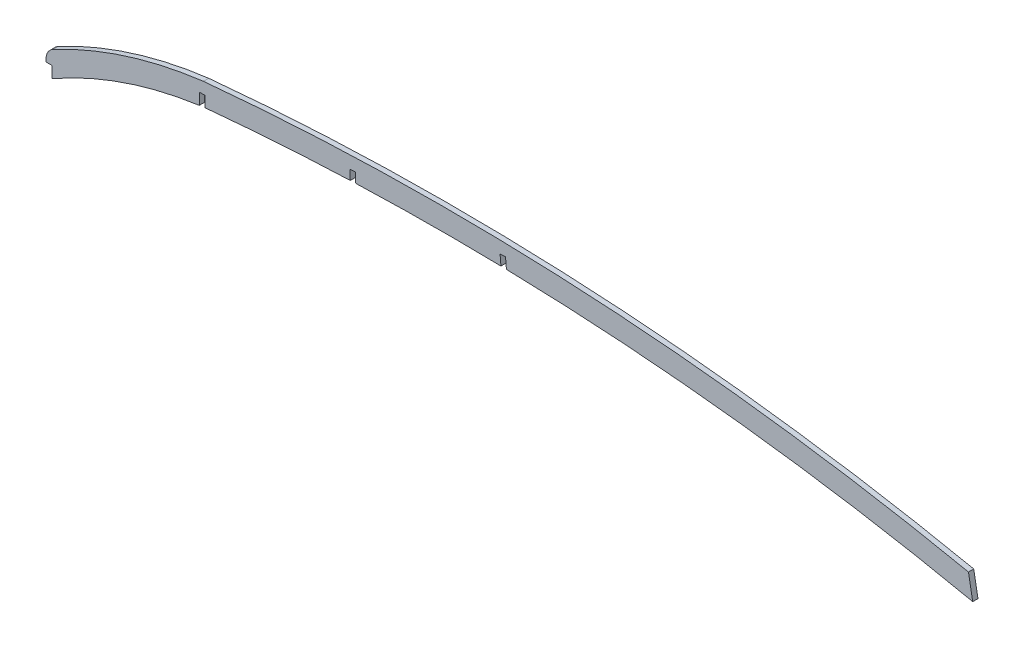
SolidWorks part; units mm, degrees
material "Balsa"
ref_plane "Front Plane" through (0, 0, 0) normal (0, 0, 1) x (1, 0, 0)
ref_plane "Top Plane" through (0, 0, 0) normal (0, 1, 0) x (1, 0, 0)
ref_plane "Right Plane" through (0, 0, 0) normal (1, 0, 0) x (0, 0, -1)
sketch "Sketch1" plane through (0, 0, 0) normal (0, 0, 1) x (1, 0, 0)
  line L0 (0, 101.6) -> (0, 100.0553)
  line L1 (0, -1.7463) -> (0, 1.7463) construction
  line L2 (0, 86.36) -> (8.1082, 86.36) construction
  line L3 (3.7499, 106.3536) -> (3.7499, -82.5359) construction
  line L4 (8.1082, 101.6) -> (0, 101.6) construction
  line L5 (92.329, 130.518) -> (92.329, 123.5672)
  line L6 (3.7499, 93.1973) -> (0, 91.0322) construction
  line L7 (0, 99.5163) -> (0, 88.039) construction
  line L8 (558.2295, 97.6273) -> (555.6382, 111.8229)
  line L9 (0, 91.0322) -> (0, 86.36) construction
  line L10 (3.7499, 93.1973) -> (3.7499, 100.0553)
  line L11 (3.7499, 100.0553) -> (0, 97.8902) construction
  line L12 (0, 97.8902) -> (0, 91.0322) construction
  line L13 (3.7499, 100.0553) -> (0, 100.0553)
  line L14 (0, 100.0553) -> (0, 97.8902) construction
  line L17 (92.3925, 137.6625) -> (92.3925, -126.4975) construction
  line L18 (95.631, 130.518) -> (95.631, 124.0109)
  line L19 (95.5675, -126.4975) -> (95.5675, 137.6625) construction
  line L20 (95.5675, 137.6297) -> (92.3925, 137.6297) construction
  line L21 (93.98, 137.6297) -> (93.98, 130.518) construction
  line L22 (92.329, 130.518) -> (95.631, 130.518)
  line L23 (92.329, 123.5672) -> (92.329, 122.506) construction
  line L24 (95.631, 124.0109) -> (95.631, 123.1918) construction
  line L26 (196.7865, -114.9693) -> (197.4984, -131.9724) construction
  line L27 (185.959, 143.6301) -> (186.671, 126.627) construction
  line L28 (193.6143, -115.1021) -> (194.3262, -132.1052) construction
  line L30 (182.7868, 143.4973) -> (183.4987, 126.4942) construction
  line L32 (185.959, 143.6301) -> (182.7868, 143.4973) construction
  line L41 (182.7868, 143.4973) -> (186.671, 126.627) construction
  line L42 (184.7289, 135.0622) -> (184.9758, 129.1656) construction
  line L43 (183.294, 129.865) -> (183.0502, 135.6897)
  line L44 (186.5939, 129.9858) -> (186.3493, 135.8278)
  line L45 (183.0502, 135.6897) -> (186.3493, 135.8278)
  line L46 (183.2948, 129.8477) -> (183.294, 129.865) construction
  line L47 (276.0995, 144.3308) -> (272.9362, 144.0585)
  line L48 (298.3406, -114.0477) -> (295.1773, -114.32)
  line L49 (274.4392, 126.5971) -> (277.6025, 126.8694)
  line L50 (272.9362, 144.0585) -> (274.4392, 126.5971)
  line L51 (295.1773, -114.32) -> (296.6804, -131.7814)
  line L52 (276.0995, 144.3308) -> (277.6025, 126.8694)
  line L53 (298.3406, -114.0477) -> (299.8437, -131.5091)
  line L54 (296.6804, -131.7814) -> (299.8437, -131.5091)
  line L57 (276.0995, 144.3308) -> (277.6025, 126.8694) construction
  line L59 (272.9362, 144.0585) -> (274.4392, 126.5971) construction
  line L60 (274.4392, 126.5971) -> (277.6025, 126.8694) construction
  line L63 (274.4392, 126.5971) -> (276.0995, 144.3308) construction
  line L64 (275.2694, 135.4639) -> (274.3291, 146.3866) construction
  line L65 (274.0318, 130.5899) -> (273.5181, 136.5576)
  line L66 (277.3525, 130.5142) -> (276.8079, 136.8408)
  line L67 (273.5181, 136.5576) -> (276.8079, 136.8408)
  line L68 (274.0627, 130.231) -> (274.0318, 130.5899) construction
  line L69 (193.6143, -115.1021) -> (196.7865, -114.9693)
  line L70 (186.671, 126.627) -> (183.4987, 126.4942)
  line L71 (194.3262, -132.1052) -> (197.4984, -131.9724)
  line L72 (185.959, 143.6301) -> (182.7868, 143.4973)
  line L73 (182.7868, 143.4973) -> (183.4987, 126.4942)
  line L74 (193.6143, -115.1021) -> (194.3262, -132.1052)
  line L75 (185.959, 143.6301) -> (186.671, 126.627)
  line L76 (276.0995, 144.3308) -> (272.9362, 144.0585)
  line L77 (194.3262, -132.1052) -> (197.4984, -131.9724) construction
  line L78 (196.7865, -114.9693) -> (197.4984, -131.9724)
  line L79 (186.671, 126.627) -> (183.4987, 126.4942) construction
  line L80 (193.6143, -115.1021) -> (196.7865, -114.9693) construction
  arc A0 (4.3005, 108.7585) -> (94.8544, 137.376) centre (127, -121.92) cw
  arc A1 (4.3005, 108.7585) -> (0, 101.6) centre (8.1082, 101.6) ccw
  arc A2 (3.7499, 93.1973) -> (0, 86.36) centre (8.1082, 86.36) ccw construction
  arc A3 (94.8544, 137.376) -> (555.6382, 111.8229) centre (240.8652, -1397) cw
  arc A4 (3.7499, 93.1973) -> (92.329, 123.5672) centre (127, -121.92) cw
  arc A5 (96.3112, 124.0967) -> (183.294, 129.865) centre (240.8652, -1397) cw
  arc A6 (10.5733, 96.9655) -> (96.3112, 124.0967) centre (127, -121.92) cw construction
  arc A7 (94.4927, 137.3434) -> (3.7499, 106.3536) centre (112.883, -64.8553) ccw construction
  arc A8 (96.3112, 124.0967) -> (552.9103, 98.7469) centre (240.8652, -1397) cw construction
  arc A9 (4.3005, 108.7585) -> (94.8544, 137.376) centre (127, -121.92) cw construction
  arc A10 (92.329, 123.5672) -> (95.631, 124.0109) centre (127, -121.92) cw construction
  arc A11 (94.8544, 137.376) -> (555.6382, 111.8229) centre (240.8652, -1397) cw construction
  arc A12 (95.631, 124.0109) -> (96.3112, 124.0967) centre (127, -121.92) cw
  arc A13 (556.7512, 105.7321) -> (99.1899, 122.2822) centre (270.5046, -1474.7614) ccw construction
  arc A14 (183.294, 129.865) -> (183.3575, 129.8673) centre (240.8652, -1397) cw construction
  arc A15 (184.9439, 129.9263) -> (185.9033, 129.9611) centre (240.8652, -1397) cw construction
  arc A16 (183.3575, 129.8673) -> (184.9439, 129.9263) centre (240.8652, -1397) cw construction
  arc A17 (185.9033, 129.9611) -> (186.5304, 129.9835) centre (240.8652, -1397) cw construction
  arc A18 (186.5939, 129.9858) -> (274.0318, 130.5899) centre (240.8652, -1397) cw
  arc A19 (186.5304, 129.9835) -> (186.5939, 129.9858) centre (240.8652, -1397) cw construction
  arc A20 (274.0957, 130.5885) -> (274.8114, 130.5728) centre (240.8652, -1397) cw construction
  arc A21 (277.3525, 130.5142) -> (558.2295, 97.6273) centre (240.8652, -1397) cw
  arc A22 (274.0318, 130.5899) -> (274.0957, 130.5885) centre (240.8652, -1397) cw construction
  arc A23 (274.8114, 130.5728) -> (277.2887, 130.5157) centre (240.8652, -1397) cw construction
  arc A24 (277.2887, 130.5157) -> (277.3525, 130.5142) centre (240.8652, -1397) cw construction
  spline S0 degree 3 poles (981.3177, 1818.2675) (1139.722, 204.4849) (873.2182, 1.0169) (565.628, -88.9106) (559.2919, -90.7077) (-121.8164, -278.7114) (-929.5333, 36.0269) (-1233.6865, -867.5095) knots -11.664502 -11.664502 -11.664502 -11.664502 0.25 0.25 0.5 0.5 27.071012 27.071012 27.071012 27.071012 only from (590.8643, -81.3536) to (514.7143, -102.4537) construction
  spline S1 degree 3 poles (1062.5522, -1662.3274) (1783.386, 752.2598) (1192.007, 51.9761) (480.6823, -110.4688) (472.1454, -112.3347) (455.0337, -115.879) (446.4591, -117.5582) (433.5613, -119.8984) (429.2558, -120.648) (422.7903, -121.7356) (420.6337, -122.0915) (417.3979, -122.6188) (416.3191, -122.7935) (329.7173, -136.7537) (244.3749, -151.8452) (-150.7518, 1789.6158) knots -20.37019 -20.37019 -20.37019 -20.37019 0.25 0.25 0.5 0.5 0.75 0.75 0.875 0.875 0.9375 0.9375 0.96875 0.96875 3.445896 3.445896 3.445896 3.445896 only from (514.7143, -102.4537) to (412.003, -123.4859) construction
  spline S2 degree 3 poles (-1526.2092, 975.8893) (-966.7298, 244.4948) (-373.5074, -121.9571) (226.7788, -133.168) (266.5142, -132.8729) (279.7628, -132.6016) (299.6408, -131.9345) (306.2677, -131.6688) (319.5231, -131.0505) (326.1536, -130.6977) (943.6584, -93.7895) (1501.3881, 309.0053) (2017.121, 1001.2295) knots -5.168103 -5.168103 -5.168103 -5.168103 0.25 0.5 0.5 0.625 0.625 0.6875 0.6875 0.75 0.75 6.511417 6.511417 6.511417 6.511417 only from (94.4926, -125.8525) to (412.003, -123.4859) construction
  spline S3 degree 3 poles (82.8406, 1879.826) (-241.5287, 509.6599) (-195.4311, -0.6421) (32.0968, -110.0953) (39.5136, -113.1375) (50.922, -117.0433) (54.7721, -118.2354) (60.6197, -119.8556) (62.5829, -120.3681) (66.5243, -121.3341) (68.5001, -121.787) (343.1899, -180.4478) (711.1357, 326.3263) (1193.75, 1513.3939) knots -7.368418 -7.368418 -7.368418 -7.368418 0.25 0.25 0.5 0.5 0.625 0.625 0.6875 0.6875 0.75 0.75 9.354609 9.354609 9.354609 9.354609 only from (3.7499, -94.8626) to (94.4926, -125.8525) construction
  spline S6 degree 3 poles (590.8643, -81.3536) (584.5771, -83.3154) (578.2709, -85.2143) (565.628, -88.9106) (559.2919, -90.7077) (540.2459, -95.9648) (527.5015, -99.2922) (514.7143, -102.4537) knots 0 0 0 0 0.25 0.25 0.5 0.5 1 1 1 1 construction
  spline S7 degree 3 poles (514.7143, -102.4537) (506.2284, -104.5517) (497.724, -106.577) (480.6823, -110.4688) (472.1454, -112.3347) (455.0337, -115.879) (446.4591, -117.5582) (433.5613, -119.8984) (429.2558, -120.648) (422.7903, -121.7356) (420.6337, -122.0915) (417.3979, -122.6188) (416.3191, -122.7935) (414.1613, -123.1413) (413.0825, -123.3155) (412.003, -123.4859) knots 0 0 0 0 0.25 0.25 0.5 0.5 0.75 0.75 0.875 0.875 0.9375 0.9375 0.96875 0.96875 1 1 1 1 construction
  spline S8 degree 3 poles (94.4926, -125.8525) (120.9278, -128.4258) (173.8258, -132.179) (226.7788, -133.168) (266.5142, -132.8729) (279.7628, -132.6016) (299.6408, -131.9345) (306.2677, -131.6688) (319.5231, -131.0505) (326.1536, -130.6977) (359.2877, -128.7173) (385.6949, -126.4433) (412.003, -123.4859) knots 0 0 0 0 0.25 0.5 0.5 0.625 0.625 0.6875 0.6875 0.75 0.75 1 1 1 1 construction
  spline S9 degree 3 poles (3.7499, -94.8626) (10.597, -99.2271) (17.6385, -103.1401) (32.0968, -110.0953) (39.5136, -113.1375) (50.922, -117.0433) (54.7721, -118.2354) (60.6197, -119.8556) (62.5829, -120.3681) (66.5243, -121.3341) (68.5001, -121.787) (78.4043, -123.9021) (86.408, -125.1172) (94.4926, -125.8525) knots 0 0 0 0 0.25 0.25 0.5 0.5 0.625 0.625 0.6875 0.6875 0.75 0.75 1 1 1 1 construction
  spline S15 degree 3 poles (587.4426, -62.5747) (587.1827, -61.1511) (586.6535, -58.2526) (585.7873, -53.5174) (584.8512, -48.394) (583.8406, -42.8532) (582.7565, -36.9006) (581.5991, -30.5376) (580.1295, -22.4773) (578.3524, -12.6853) (576.2505, -1.1976) (574.1192, 10.4518) (571.9272, 22.5233) (569.819, 34.0829) (567.7342, 45.5019) (565.8232, 55.9911) (564.3841, 63.8754) (563.4512, 68.9947) (562.9209, 71.9076) (562.4102, 74.7138) (561.9192, 77.4122) (561.4478, 80.0018) (560.9959, 82.4822) (560.5637, 84.8528) (560.1512, 87.1138) (559.7582, 89.2651) (559.385, 91.3073) (559.0312, 93.2414) (558.6975, 95.0661) (558.3822, 96.7905) (558.1867, 97.8615) (558.0896, 98.3936) knots 0 0 0 0 0.031687 0.064515 0.098497 0.133644 0.169967 0.207478 0.246191 0.30842 0.370332 0.432609 0.495165 0.563925 0.620591 0.686243 0.746551 0.766006 0.785258 0.804303 0.823142 0.841774 0.860197 0.878411 0.896416 0.91421 0.931793 0.949164 0.966322 0.983268 1 1 1 1 construction
  point P53 (93.98, 130.518)
  dimension "D4" = 8.1082
  dimension "D2" = 127
  dimension "D8" = 1397
  dimension "D9" = 30
  dimension "D1" = 15.24
  dimension "D3" = 8.1082
  dimension "D5" = 8.1082
  dimension "D6" = 101.6
  dimension "D7" = 121.92
  dimension "D10" = 6.858
  dimension "D11" = 3.7499
  dimension "D12" = 3.302
  dimension "D13" = 6.858
  dimension "D14" = 3.302
  dimension "D15" = 5.842
  dimension "D16" = 3.302
  dimension "D17" = 6.35
extrude "Boss-Extrude1" add sketch "Sketch1" along normal mid plane 3.175 contours L66 A21 L8 A3 A0 A1 L0 L13 L10 A4 L5 L22 L18 A12 A5 L43 L45 L44 A18 L65 L67 region at (90.7898, 125.7592, 0) region at (184.5418, 139.5154, 0) region at (229.8823, 137.3776, 0) region at (274.8389, 140.3189, 0) region at (417.3374, 125.2624, 0)
equation "\"slotwidth\"=0.167708"
